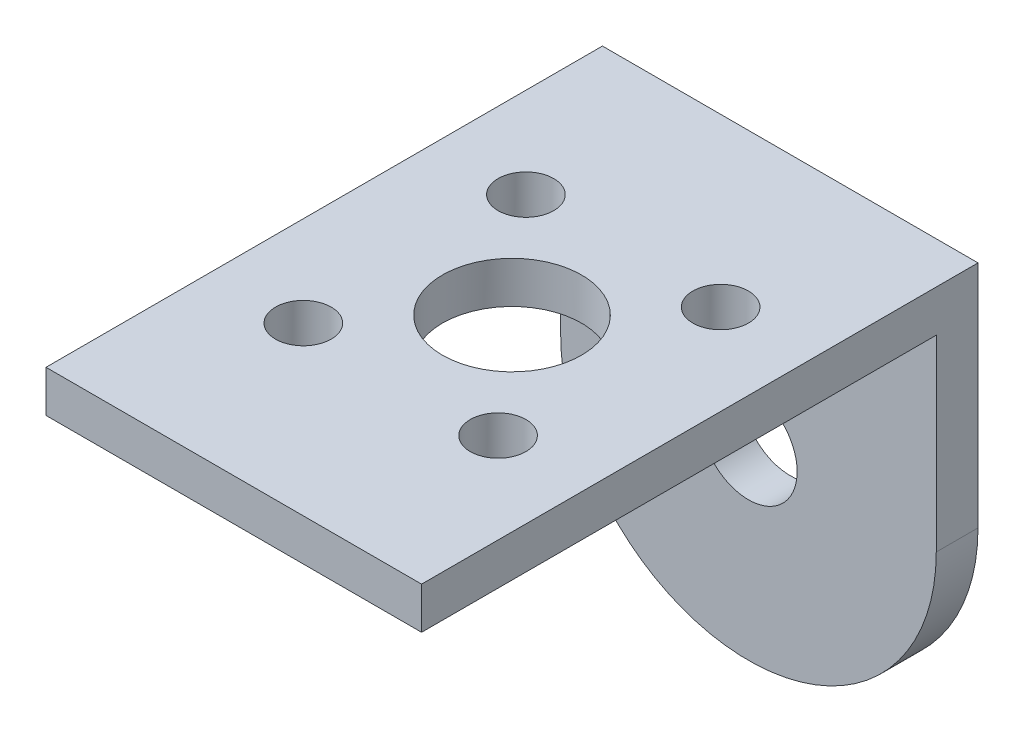
SolidWorks part; units mm, degrees
ref_plane "前视基准面" through (0, 0, 0) normal (0, 0, 1) x (1, 0, 0)
ref_plane "上视基准面" through (0, 0, 0) normal (0, 1, 0) x (1, 0, 0)
ref_plane "右视基准面" through (0, 0, 0) normal (1, 0, 0) x (0, 0, -1)
sketch "Model" plane through (0, 0, 0) normal (0, 0, 1) x (1, 0, 0)
  line L0 (2619.7667, 1592.8264) -> (2619.7667, 1609.3264)
  line L1 (2592.7667, 1592.8264) -> (2592.7667, 1609.3264)
  line L2 (2592.7667, 1609.3264) -> (2619.7667, 1609.3264)
  circle A0 centre (2606.2667, 1592.8264) radius 3.5
  arc A1 (2592.7667, 1592.8264) -> (2619.7667, 1592.8264) centre (2606.2667, 1592.8264) ccw
  dimension "D1" = 16.5
extrude "凸台-拉伸1" add sketch "Model" along normal blind 40
sketch "草图3" plane through (2619.7667, 0, 0) normal (1, 0, 0) x (0, 0, -1)
  line L0 (-40, 1592.8264) -> (-40, 1609.3264) construction
  line L1 (-40, 1606.3264) -> (-3, 1606.3264)
  line L2 (-40, 1606.3264) -> (-40, 1569.3264)
  line L3 (-40, 1569.3264) -> (-3, 1569.3264)
  line L4 (-3, 1606.3264) -> (-3, 1569.3264)
  line L5 (-40, 1609.3264) -> (0, 1609.3264) construction
  line L6 (0, 1592.8264) -> (0, 1609.3264) construction
  dimension "D1" = 3
  dimension "D2" = 3
  dimension "D3" = 40
extrude "切除-拉伸1" cut sketch "草图3" against normal blind 40
sketch "草图4" plane through (0, 1609.3264, 0) normal (0, 1, 0) x (1, 0, 0)
  line L0 (2619.7667, 0) -> (2592.7667, 0) construction
  line L1 (2606.2667, 0) -> (2606.2667, -50000) construction
  circle A0 centre (2599.2667, -28) radius 2
  circle A1 centre (2613.2667, -28) radius 2
  circle A2 centre (2599.2667, -12) radius 2
  circle A3 centre (2613.2667, -12) radius 2
  point P5 (2606.2667, 0)
  dimension "D1" = 4
  dimension "D2" = 16
  dimension "D3" = 12
  dimension "D4" = 7
  dimension "D5" = 7
extrude "切除-拉伸2" cut sketch "草图4" against normal blind 40 contours A0 | A1 | A3 | A2
sketch "Sketch2" plane through (0, 1609.3264, 0) normal (0, 1, 0) x (1, 0, 0)
  line L0 (2606.2667, 0) -> (2606.2667, -50000) construction
  line L1 (2619.7667, 0) -> (2592.7667, 0) construction
  line L3 (2611.7667, -28) -> (-47388.2333, -28) construction
  line L4 (2611.7667, -12) -> (-47388.2333, -12) construction
  circle A0 centre (2606.2667, -20) radius 5
  point P4 (2606.2667, 0)
  dimension "D1" = 10
  dimension "D2" = 8
extrude "Cut-Extrude1" cut sketch "Sketch2" against normal blind 10
